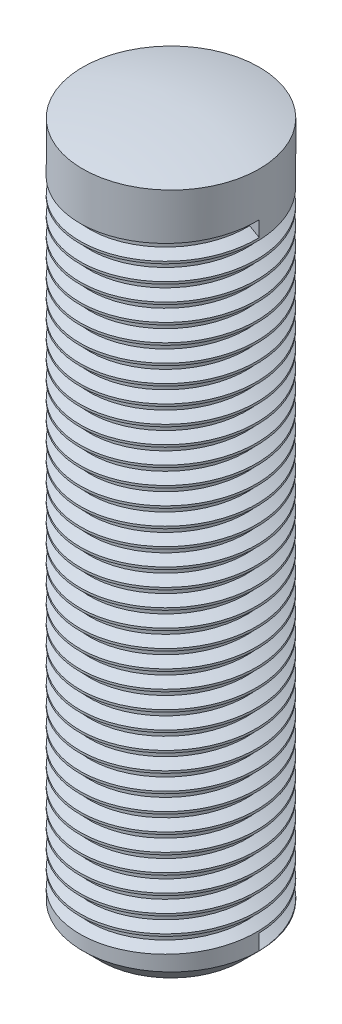
SolidWorks part; units mm, degrees
material "AISI 1045 钢，冷拔"
ref_plane "前视基准面" through (0, 0, 0) normal (0, 0, 1) x (1, 0, 0)
ref_plane "上视基准面" through (0, 0, 0) normal (0, 1, 0) x (1, 0, 0)
ref_plane "右视基准面" through (0, 0, 0) normal (1, 0, 0) x (0, 0, -1)
sketch "草图1" plane through (0, 0, 0) normal (0, 0, 1) x (1, 0, 0)
  line L0 (0, -12.6562) -> (0, 27.3438)
  line L1 (0, 27.3438) -> (5, 27.3438) construction
  line L2 (0, -12.6562) -> (5, -12.6562)
  line L3 (5, -12.6562) -> (5, 26.7087)
  arc A0 (5, 26.7087) -> (0, 27.3438) centre (0, 7.3438) ccw
  dimension "D3" = 20
  dimension "D1" = 5
  dimension "D2" = 40
revolve "旋转1" add sketch "草图1" angle 360 about L0
chamfer "倒角1" distance 1 angle 45 1 edges at (0, -12.6562, -5)
thread "螺纹线1" pitch 1 method cut trim with start face yes trim with end face yes profile "螺纹线轮廓1" start angle 0, offset 0, length 35, pitch 1, diameter 10
ref_plane "基准面1" through (5, -11.6562, 0) normal (0, 0, 1) x (1, 0, 0)
sketch "螺纹线轮廓1" plane through (5, -11.6562, 0) normal (0, 0, 1) x (1, 0, 0)
  line L0 (0, 0) -> (0, 1) construction
  line L11 (0, 0) -> (0, 0.875)
  line L12 (0, 0.875) -> (-0.5413, 0.5625)
  line L13 (-0.5413, 0.5625) -> (-0.5413, 0.3125)
  line L15 (-0.5413, 0.3125) -> (0, 0)
  line L17 (-0.5413, 0.4375) -> (0, 0.4375) construction
  point P2 (0, 0)
  dimension "Pitch" = 1
  dimension "Profile_Angle" = 60
  dimension "Profile_Land" = 0.25
  dimension "Profile_Height" = 0.5413
